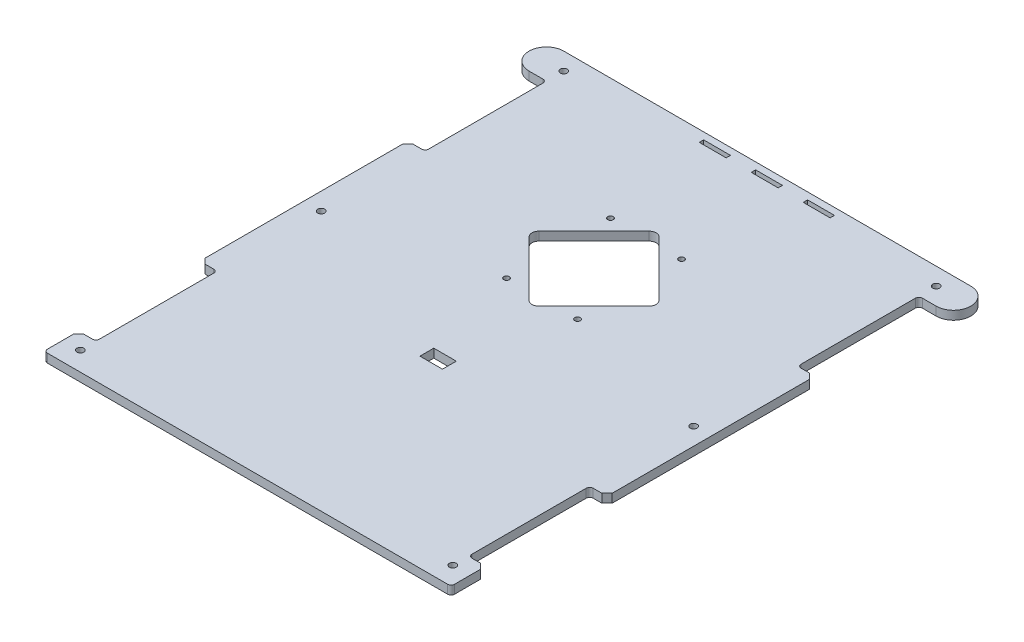
SolidWorks part; units mm, degrees
material "Teak"
ref_plane "Front Plane" through (0, 0, 0) normal (0, 0, 1) x (1, 0, 0)
ref_plane "Top Plane" through (0, 0, 0) normal (0, 1, 0) x (1, 0, 0)
ref_plane "Right Plane" through (0, 0, 0) normal (1, 0, 0) x (0, 0, -1)
sketch "Sketch1" plane through (0, 0, 0) normal (0, 1, 0) x (1, 0, 0)
  line L0 (0, 190) -> (0, -110) construction
  line L1 (-117.5, 0) -> (117.5, 0) construction
  line L2 (-117.5, -110) -> (117.5, -110)
  line L3 (117.5, -110) -> (117.5, -90)
  line L4 (117.5, -90) -> (107.5, -90)
  line L5 (107.5, -90) -> (107.5, -20)
  line L6 (107.5, -20) -> (117.5, -20)
  line L7 (117.5, -20) -> (117.5, 100)
  line L8 (117.5, 100) -> (107.5, 100)
  line L9 (107.5, 100) -> (107.5, 170)
  line L10 (107.5, 170) -> (127.5, 170)
  line L11 (-107.5, 170) -> (-127.5, 170)
  line L12 (-107.5, 100) -> (-107.5, 170)
  line L13 (-117.5, 100) -> (-107.5, 100)
  line L14 (-117.5, -20) -> (-117.5, 100)
  line L15 (-107.5, -20) -> (-117.5, -20)
  line L16 (-107.5, -90) -> (-107.5, -20)
  line L17 (-117.5, -90) -> (-107.5, -90)
  line L18 (-117.5, -110) -> (-117.5, -90)
  line L19 (127.5, 170) -> (127.5, 190)
  line L20 (127.5, 190) -> (-127.5, 190)
  line L21 (-127.5, 170) -> (-127.5, 190)
  point P5 (0, 0)
  dimension "D1" = 20
  dimension "D2" = 300
  dimension "D3" = 110
  dimension "D4" = 20
  dimension "D5" = 10
  dimension "D6" = 70
  dimension "D7" = 70
  dimension "D8" = 255
  dimension "D9" = 20
extrude "Boss-Extrude1" add sketch "Sketch1" along normal blind 5
fillet "Fillet3" 2 edges at (127.5, 2.5, -170) (127.5, 2.5, -190) type full round first side face at (117.5, 2.5, -170) second side face at (0, 2.5, -190) middle face at (127.5, 2.5, -180)
fillet "Fillet4" 2 edges at (-127.5, 2.5, -190) (-127.5, 2.5, -170) type full round first side face at (-5, 2.5, -190) second side face at (-117.5, 2.5, -170) middle face at (-127.5, 2.5, -180)
fillet "Fillet2" radius 2 10 edges at (107.5, 2.5, 20) (107.5, 2.5, -170) (107.5, 2.5, -100) (107.5, 2.5, 90) (-107.5, 2.5, -100) (-107.5, 2.5, 90) (-107.5, 2.5, 20) (-107.5, 2.5, -170) (-117.5, 2.5, 110) (117.5, 2.5, 110)
sketch "Sketch2" plane through (0, 5, 0) normal (0, 1, 0) x (1, 0, 0)
  line L0 (0, -110) -> (0, 90) construction
  line L1 (-115.5, -110) -> (115.5, -110) construction
  line L2 (107.5, 102) -> (107.5, 168) construction
  line L4 (117.5, -20) -> (117.5, 100) construction
  line L5 (117.5, -108) -> (117.5, -90) construction
  arc A0 (117.5, 170) -> (117.5, 190) centre (117.5, 180) ccw construction
  circle A1 centre (107.5, 180) radius 2
  circle A2 centre (107.5, 40) radius 2
  circle A3 centre (107.5, -99) radius 2
  circle A5 centre (-107.5, -99) radius 2
  circle A6 centre (-107.5, 40) radius 2
  circle A7 centre (-107.5, 180) radius 2
  point P17 (127.5, 180)
  point P26 (117.5, 40)
  point P30 (117.5, -99)
  dimension "D1" = 4
  dimension "D3" = 10
extrude "layer fix hole" cut sketch "Sketch2" against normal through all
sketch "Sketch3" plane through (0, 5, 0) normal (0, 1, 0) x (1, 0, 0)
  line L0 (0, 190) -> (0, -110) construction
  line L1 (117.5, 190) -> (-117.5, 190) construction
  line L2 (-115.5, -110) -> (115.5, -110) construction
  line L3 (-34.6482, 92.8284) -> (-2.8284, 124.6482)
  line L8 (-26.5, 126) -> (26.5, 126) construction
  line L9 (-26.5, 126) -> (-26.5, 54) construction
  line L14 (-26.5, 54) -> (26.5, 54) construction
  line L15 (26.5, 126) -> (26.5, 54) construction
  line L21 (-26.5, 126) -> (26.5, 54) construction
  line L22 (-26.5, 54) -> (26.5, 126) construction
  line L23 (-34.6482, 87.1716) -> (-2.8284, 55.3518)
  line L24 (2.8284, 124.6482) -> (34.6482, 92.8284)
  line L25 (2.8284, 55.3518) -> (34.6482, 87.1716)
  line L26 (-37.4767, 90) -> (37.4767, 90) construction
  line L27 (0, 127.4767) -> (0, 52.5233) construction
  circle A12 centre (20.5, 120) radius 1.6
  circle A13 centre (20.5, 60) radius 1.6
  circle A14 centre (-20.5, 60) radius 1.6
  circle A15 centre (-20.5, 120) radius 1.6
  arc A16 (-2.8284, 124.6482) -> (2.8284, 124.6482) centre (0, 121.8198) cw
  arc A17 (34.6482, 92.8284) -> (34.6482, 87.1716) centre (31.8198, 90) cw
  arc A18 (-2.8284, 55.3518) -> (2.8284, 55.3518) centre (0, 58.1802) ccw
  arc A19 (-34.6482, 87.1716) -> (-34.6482, 92.8284) centre (-31.8198, 90) cw
  point P6 (0, 90)
  point P19 (0, 54.1802)
  point P20 (0, 90)
  point P21 (-18.7383, 108.7383)
  point P22 (18.7383, 71.2617)
  point P23 (0, 125.8198)
  dimension "D3" = 3.2
  dimension "D2" = 53
  dimension "D9" = 6
  dimension "D14" = 4
  dimension "D1" = 72
  dimension "D4" = 6
  dimension "D5" = 6
  dimension "D6" = 6
  dimension "D7" = 6
  dimension "D8" = 6
  dimension "D10" = 6
  dimension "D11" = 6
  dimension "D12" = 53
  dimension "D13" = 100
  dimension "D15" = 35.8198
  dimension "D16" = 35.8198
extrude "arm fix hole" cut sketch "Sketch3" against normal through all
sketch "Sketch4" plane through (0, 5, 0) normal (0, 1, 0) x (1, 0, 0)
  line L0 (0, 0) -> (0, 190) construction
  line L1 (117.5, 190) -> (-117.5, 190) construction
  line L2 (-32.75, 186) -> (-32.75, 183.5)
  line L3 (-72.75, 186) -> (-57.25, 186)
  line L4 (-72.75, 186) -> (-72.75, 183.5)
  line L5 (-72.75, 183.5) -> (-57.25, 183.5)
  line L6 (-57.25, 186) -> (-57.25, 183.5)
  line L7 (-17.25, 183.5) -> (-32.75, 183.5)
  line L8 (-17.25, 186) -> (-17.25, 183.5)
  line L9 (-17.25, 186) -> (-32.75, 186)
  line L10 (5, 97.0905) -> (5, 68.2589) construction
  line L11 (-85, 183.5) -> (85, 183.5) construction
  line L12 (-85, 183.5) -> (-85, 186) construction
  line L13 (-85, 186) -> (85, 186) construction
  line L14 (85, 183.5) -> (85, 186) construction
  line L15 (-25, 68.2589) -> (-25, 97.0905) construction
  line L16 (-65, 97.0905) -> (-65, 68.2589) construction
  line L17 (-25, 68.2589) -> (-25, 97.0905) construction
  line L18 (35, 68.2589) -> (35, 97.0905) construction
  line L20 (-2.75, 183.5) -> (12.75, 183.5)
  line L21 (-2.75, 183.5) -> (-2.75, 186)
  line L22 (-2.75, 186) -> (12.75, 186)
  line L23 (12.75, 183.5) -> (12.75, 186)
  line L24 (27.25, 183.5) -> (42.75, 183.5)
  line L25 (27.25, 183.5) -> (27.25, 186)
  line L26 (27.25, 186) -> (42.75, 186)
  line L27 (42.75, 183.5) -> (42.75, 186)
  point P17 (-65, 183.5)
  point P25 (-25, 183.5)
  point P35 (5, 186)
  point P36 (35, 186)
  dimension "D1" = 15.5
  dimension "D2" = 2.5
  dimension "D3" = 4
  dimension "D4" = 20
  dimension "D5" = 170
  dimension "D6" = 60
  dimension "D7" = 90
  dimension "D8" = 120
extrude "IR fix hole" cut sketch "Sketch4" against normal through all
chamfer "Chamfer1" distance 3 angle 45 6 edges at (117.5, 2.5, 20) (-117.5, 2.5, -100) (-117.5, 2.5, 20) (-117.5, 2.5, 90) (117.5, 2.5, -100) (117.5, 2.5, 90)
sketch "Sketch5" plane through (0, 5, 0) normal (0, 1, 0) x (1, 0, 0)
  line L1 (-57.25, 183.5) -> (-72.75, 183.5)
  line L2 (-57.25, 183.5) -> (-57.25, 186)
  line L3 (-57.25, 186) -> (-72.75, 186)
  line L4 (-72.75, 183.5) -> (-72.75, 186)
extrude "Boss-Extrude2" add sketch "Sketch5" against normal up to surface (5 mm away) up to face at (-65, 0, -184.75)
sketch "Sketch6" plane through (0, 5, 0) normal (0, 1, 0) x (1, 0, 0)
  line L0 (0, 110) -> (0, -110) construction
  line L1 (-115.5, -110) -> (115.5, -110) construction
  line L3 (6.5, -4) -> (-6.5, -4)
  line L4 (6.5, -4) -> (6.5, 4)
  line L5 (6.5, 4) -> (-6.5, 4)
  line L6 (-6.5, -4) -> (-6.5, 4)
  line L7 (6.5, -4) -> (-6.5, 4) construction
  line L8 (6.5, 4) -> (-6.5, -4) construction
  point P0 (0, 0)
  point P6 (0, 0)
  dimension "D1" = 13
  dimension "D2" = 8
extrude "Turn on/off Switch " cut sketch "Sketch6" against normal up to next
